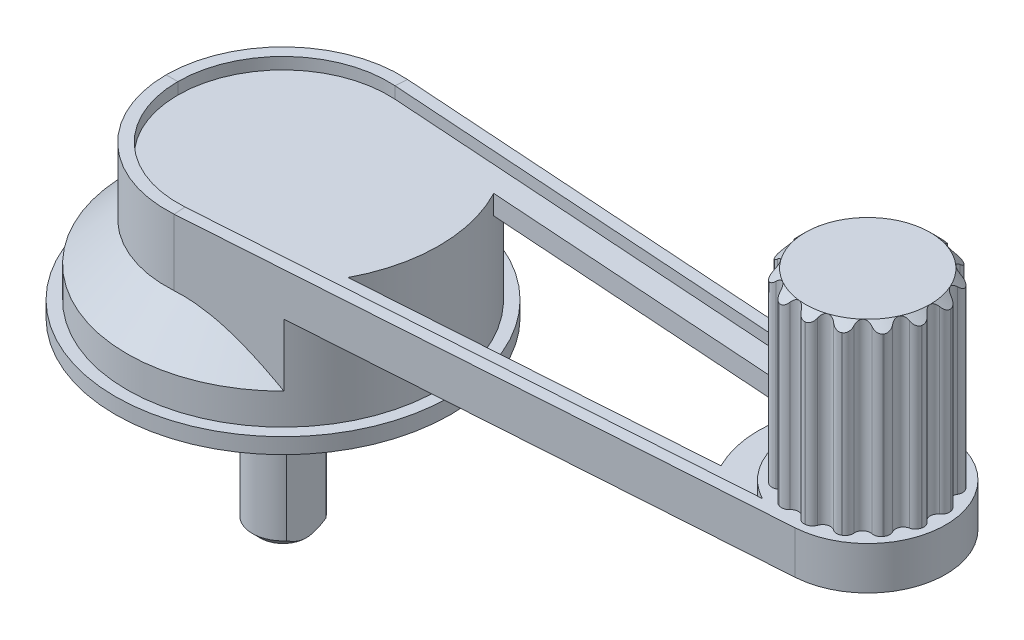
SolidWorks part; units mm, degrees
ref_plane "前视基准面" through (0, 0, 0) normal (0, 0, 1) x (1, 0, 0)
ref_plane "上视基准面" through (0, 0, 0) normal (0, 1, 0) x (1, 0, 0)
ref_plane "右视基准面" through (0, 0, 0) normal (1, 0, 0) x (0, 0, -1)
sketch "草图1" plane through (0, 0, 0) normal (0, 0, 1) x (1, 0, 0)
  line L0 (0, 0) -> (0, -15184.8005) construction
  line L1 (0, 0) -> (15184.8005, 0) construction
  line L2 (0, 0) -> (-3.925, 0)
  line L3 (-3.925, 0) -> (-3.925, 20)
  line L4 (-3.925, 20) -> (-11.5, 20)
  line L5 (-11.5, 20) -> (-11.5, 23)
  line L6 (-11.5, 23) -> (-21.5, 23)
  line L7 (-21.5, 23) -> (-21.5, 25)
  line L8 (-21.5, 25) -> (-20, 25)
  line L9 (-20, 25) -> (-20, 29)
  line L10 (-20, 29) -> (-15, 34)
  line L11 (-15, 34) -> (0, 34)
  line L12 (0, 34) -> (0, 0)
  dimension "D1" = 5
  dimension "D2" = 29
  dimension "D3" = 25
  dimension "D4" = 23
  dimension "D5" = 20
  dimension "D6" = 7.85
  dimension "D7" = 23
  dimension "D8" = 43
  dimension "D9" = 40
  dimension "D10" = 45
revolve "旋转1" add sketch "草图1" angle 360 about L0
sketch "草图2" plane through (0, 0, 0) normal (0, 0, 1) x (1, 0, 0)
  line L0 (-15, 42.5) -> (-15, 37)
  line L1 (-15, 37) -> (-13.5, 37)
  line L2 (-13.5, 37) -> (-13.5, 38.5)
  line L3 (-13.5, 38.5) -> (-10.5, 38.5)
  line L4 (-10.5, 38.5) -> (-10.5, 41)
  line L5 (-10.5, 41) -> (-13.5, 41)
  line L6 (-13.5, 41) -> (-13.5, 42.5)
  line L7 (-13.5, 42.5) -> (-15, 42.5)
  line L8 (0, 0) -> (0, -50000) construction
  line L9 (-3.925, 0) -> (3.925, 0) construction
  dimension "D1" = 5.5
  dimension "D2" = 42.5
  dimension "D3" = 15
  dimension "D4" = 2.5
  dimension "D5" = 4.5
  dimension "D6" = 1.5
ref_plane "基准面1" through (0, 42.5, 0) normal (0, 1, 0) x (1, 0, 0)
sketch "草图3" plane through (0, 42.5, 0) normal (0, 1, 0) x (1, 0, 0)
  line L0 (0, 0) -> (75, 0) construction
  line L1 (1, 14.9666) -> (75.6667, 9.9778)
  line L2 (1, -14.9666) -> (75.6667, -9.9778)
  arc A0 (1, 14.9666) -> (1, -14.9666) centre (0, 0) ccw
  arc A1 (75.6667, -9.9778) -> (75.6667, 9.9778) centre (75, 0) ccw
  dimension "D2" = 15
  dimension "D3" = 10
  dimension "D1" = 75
sweep "扫描1" add profiles "草图2" path "草图3"
sketch "草图4" plane through (0, 34, 0) normal (0, 1, 0) x (1, 0, 0)
  line L0 (75.6667, -9.9778) -> (1, -14.9666) construction
  line L1 (1, 14.9666) -> (75.6667, 9.9778) construction
  line L2 (14.1993, -14.0847) -> (1, -14.9666)
  line L3 (1, 14.9666) -> (14.1993, 14.0847)
  arc A0 (-15, 0) -> (1, -14.9666) centre (0, 0) ccw construction
  arc A1 (1, 14.9666) -> (-15, 0) centre (0, 0) ccw construction
  arc A2 (-15, 0) -> (1, -14.9666) centre (0, 0) ccw
  arc A3 (1, 14.9666) -> (-15, 0) centre (0, 0) ccw
  circle A5 centre (0, 0) radius 20 construction
  arc A6 (14.1993, -14.0847) -> (14.1993, 14.0847) centre (0, 0) ccw
extrude "凸台-拉伸1" add sketch "草图4" along normal up to surface (7 mm away) and the other way up to surface (9 mm away) up to face at (-6.8988, 41, -7.3751) other way up to face at (0, 25, 21.5)
sketch "草图5" plane through (0, 37, 0) normal (0, -1, 0) x (1, 0, 0)
  circle A0 centre (75, 0) radius 10
  arc A1 (75.6667, -9.9778) -> (75.6667, 9.9778) centre (75, 0) ccw construction
extrude "凸台-拉伸2" add sketch "草图5" against normal up to surface (5.5 mm away) up to face at (79.9333, 42.5, 0)
sketch "草图6" plane through (0, 38.5, 0) normal (0, -1, 0) x (1, 0, 0)
  line L0 (14.1993, -14.0847) -> (75.6667, -9.9778) construction
  line L1 (75.6667, 9.9778) -> (14.1993, 14.0847) construction
  line L2 (65.8905, -10.631) -> (75.6667, -9.9778)
  line L3 (75.6667, 9.9778) -> (65.8905, 10.631)
  arc A0 (65.8905, -10.631) -> (65.8905, 10.631) centre (75, 0) cw
  arc A1 (70.3106, 8.8323) -> (70.3106, -8.8323) centre (75, 0) ccw construction
  arc A2 (75.6667, 9.9778) -> (75.6667, -9.9778) centre (75, 0) ccw
  dimension "D1" = 14
extrude "凸台-拉伸3" add sketch "草图6" against normal up to surface (2.5 mm away)
sketch "草图7" plane through (0, 42.5, 0) normal (0, 1, 0) x (1, 0, 0)
  circle A0 centre (75, 0) radius 9
  dimension "D1" = 18
extrude "凸台-拉伸4" add sketch "草图7" along normal blind 23.5
chamfer "倒角1" distance 1 angle 45 1 edges at (75, 66, 9)
sketch "草图8" plane through (0, 66, 0) normal (0, 1, 0) x (1, 0, 0)
  line L0 (75, 0) -> (84, 0) construction
  circle A0 centre (75, 0) radius 9 construction
  circle A1 centre (84, 0) radius 1
  dimension "D1" = 2
extrude "切除-拉伸1" cut sketch "草图8" against normal blind 23.5
fillet "圆角1" radius 1 2 edges at (83.9444, 53.75, 0.9985) (83.9444, 53.75, -0.9985)
pattern_circular "阵列(圆周)1" count 15 over 360 about axis through (75, 66, 0) along (0, -1, 0) of "切除-拉伸1", "圆角1"
sketch "草图9" plane through (0, 0, 0) normal (0, -1, 0) x (1, 0, 0)
  line L1 (2.975, 7.8847) -> (6.8905, 7.8847)
  line L2 (2.975, 7.8847) -> (2.975, -8.3138)
  line L3 (2.975, -8.3138) -> (6.8905, -8.3138)
  line L4 (6.8905, 7.8847) -> (6.8905, -8.3138)
  circle A1 centre (0, 0) radius 3.925 construction
  dimension "D1" = 6.9
extrude "切除-拉伸2" cut sketch "草图9" against normal up to surface (20 mm away) up to face at (0, 20, 3.925)
chamfer "倒角2" distance 1 angle 45 2 edges at (-3.925, 0, 0) (0, 23, 11.5)
